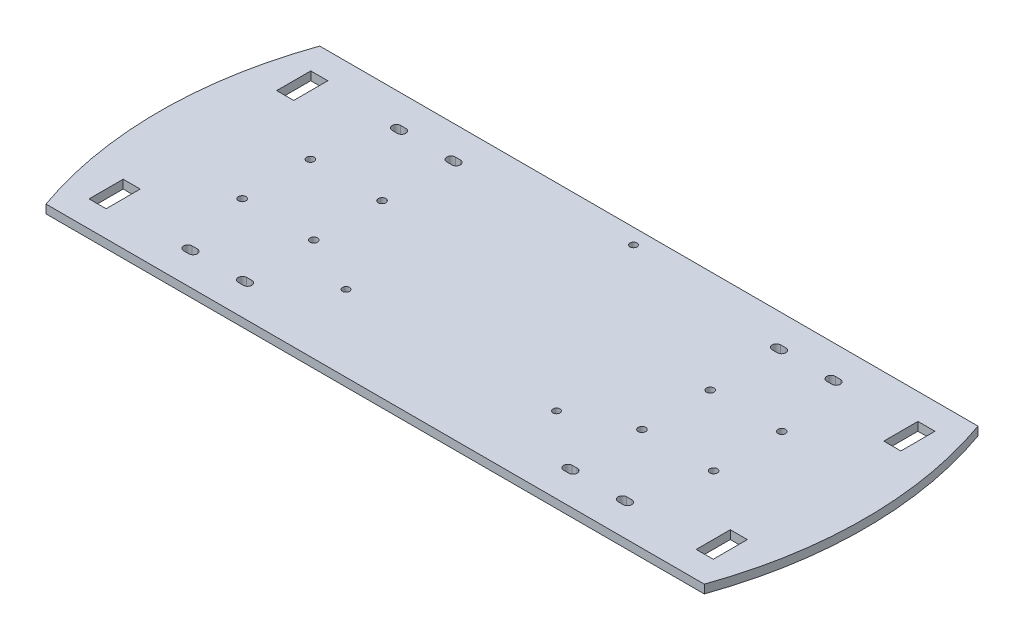
SolidWorks part; units mm, degrees
ref_plane "前基準面" through (0, 0, 0) normal (0, 0, 1) x (1, 0, 0)
ref_plane "上基準面" through (0, 0, 0) normal (0, 1, 0) x (1, 0, 0)
ref_plane "右基準面" through (0, 0, 0) normal (1, 0, 0) x (0, 0, -1)
sketch "草圖1" plane through (0, 0, 0) normal (0, 1, 0) x (1, 0, 0)
  line L0 (0, 0) -> (0, 89.692) construction
  line L1 (0, 0) -> (84.1488, -48.5834) construction
  line L2 (0, 0) -> (-79.0259, -45.6256) construction
  line L3 (183, -45) -> (173, -45)
  line L4 (193, -80.25) -> (-193, -80.25)
  line L5 (193, -80.25) -> (193, 80.25) construction
  line L6 (193, 80.25) -> (-193, 80.25)
  line L7 (-193, -80.25) -> (-193, 80.25) construction
  line L8 (0, 80.25) -> (0, -80.25) construction
  line L9 (193, 0) -> (-193, 0) construction
  line L10 (-155, -100) -> (155, -100) construction
  line L11 (-155, -100) -> (-155, 100) construction
  line L12 (-155, 100) -> (155, 100) construction
  line L13 (155, -100) -> (155, 100) construction
  line L14 (0, 100) -> (0, -100) construction
  line L15 (-155, 0) -> (155, 0) construction
  line L16 (-156, -22) -> (-172, -22) construction
  line L17 (-156, -22) -> (-156, 22) construction
  line L18 (-156, 22) -> (-172, 22) construction
  line L19 (-172, -22) -> (-172, 22) construction
  line L20 (-173, -80) -> (-183, -80) construction
  line L21 (-156, 0) -> (-172, 0) construction
  line L22 (-173, -80) -> (-173, 80) construction
  line L23 (-173, 80) -> (-183, 80) construction
  line L24 (-183, -80) -> (-183, 80) construction
  line L25 (-183, -65) -> (-173, -65)
  line L26 (-173, 0) -> (-183, 0) construction
  line L27 (-183, -65) -> (-183, -45)
  line L28 (-183, -45) -> (-173, -45)
  line L29 (-173, -65) -> (-173, -45)
  line L30 (-183, 45) -> (-173, 45)
  line L31 (-183, 45) -> (-183, 65)
  line L32 (-183, 65) -> (-173, 65)
  line L33 (-173, 45) -> (-173, 65)
  line L34 (173, -65) -> (173, -45)
  line L35 (183, -65) -> (173, -65)
  line L36 (183, -65) -> (183, -45)
  line L37 (183, 65) -> (173, 65)
  line L38 (173, 45) -> (173, 65)
  line L39 (183, 45) -> (173, 45)
  line L40 (183, 45) -> (183, 65)
  circle A0 centre (0, 71.25) radius 4 construction
  circle A4 centre (61.7043, -35.625) radius 4 construction
  circle A6 centre (-61.7043, -35.625) radius 4 construction
  circle A7 centre (0, 71.25) radius 2.05
  circle A8 centre (61.7043, -35.625) radius 2.05
  circle A9 centre (-61.7043, -35.625) radius 2.05
  circle A11 centre (0, 0) radius 75.25 construction
  circle A12 centre (0, 0) radius 80.25 construction
  arc A13 (-193, 80.25) -> (-193, -80.25) centre (33.1856, 0) ccw
  arc A14 (193, 80.25) -> (193, -80.25) centre (-33.1856, 0) cw
  point P22 (-164, 0)
  point P33 (-178, 0)
  point P62 (206.8144, 0)
  point P63 (-206.8144, 0)
  dimension "D3" = 4.1
  dimension "D4" = 8
  dimension "D5" = 71.25
  dimension "D6" = 120
  dimension "D1" = 120
  dimension "D9" = 5
  dimension "D22" = 4.1
  dimension "D23" = 240
  dimension "D2" = 71.25
  dimension "D7" = 71.25
  dimension "D8" = 310
  dimension "D10" = 200
  dimension "D11" = 16
  dimension "D12" = 44
  dimension "D13" = 1
  dimension "D14" = 10
  dimension "D15" = 160
  dimension "D16" = 1
  dimension "D17" = 10
  dimension "D18" = 386
  dimension "D19" = 20
  dimension "D20" = 15
  dimension "D21" = 15
  dimension "D24" = 413.6287
extrude "填料-伸長1" add sketch "草圖1" along normal blind 5
sketch "草圖2" plane through (0, 5, 0) normal (0, 1, 0) x (1, 0, 0)
  line L0 (-232.8206, 0) -> (229.5414, 0) construction
  line L1 (0, 102.2006) -> (0, -106.5728) construction
  line L2 (-54.2, 28.5) -> (-151.2, 28.5)
  line L3 (-54.2, 28.5) -> (-54.2, -28.5)
  line L4 (-54.2, -28.5) -> (-151.2, -28.5)
  line L5 (-151.2, 28.5) -> (-151.2, -28.5)
  line L6 (-102.7, -28.5) -> (-102.7, 28.5) construction
  line L7 (-54.2, 0) -> (-151.2, 0) construction
  line L8 (-173, -65) -> (-173, -45) construction
  line L9 (-172.2, 4) -> (-151.2, 4)
  line L10 (-172.2, 4) -> (-172.2, -4) construction
  line L11 (-172.2, -4) -> (-151.2, -4)
  line L12 (-151.2, 4) -> (-151.2, -4)
  line L13 (-172, 15) -> (-154.9, 15)
  line L14 (-172.2, 0) -> (-151.2, 0) construction
  line L15 (-172, 15) -> (-172, -15)
  line L16 (-172, -15) -> (-154.9, -15)
  line L17 (-154.9, 15) -> (-154.9, -15)
  line L18 (172, -15) -> (154.9, -15)
  line L19 (154.9, 15) -> (154.9, -15)
  line L20 (172, 15) -> (154.9, 15)
  line L21 (172, 15) -> (172, -15)
  line L22 (172.2, -4) -> (151.2, -4)
  line L23 (151.2, 4) -> (151.2, -4)
  line L24 (172.2, 4) -> (151.2, 4)
  line L25 (172.2, 4) -> (172.2, -4)
  line L26 (54.2, -28.5) -> (151.2, -28.5)
  line L27 (151.2, 28.5) -> (151.2, -28.5)
  line L28 (54.2, 28.5) -> (151.2, 28.5)
  line L29 (54.2, 28.5) -> (54.2, -28.5)
  line L30 (193, 80.25) -> (-193, 80.25) construction
  line L31 (-183, 80.25) -> (-173, 80.25) construction
  line L32 (-183, 80.25) -> (-183, -80.25) construction
  line L33 (-183, -80.25) -> (-173, -80.25) construction
  line L34 (-173, 80.25) -> (-173, -80.25) construction
  line L35 (-193, -80.25) -> (193, -80.25) construction
  line L36 (-183, 65) -> (-183, 45) construction
  line L37 (183, 80.25) -> (183, -80.25) construction
  line L38 (173, 80.25) -> (173, -80.25) construction
  point P3 (-102.7, 0)
  point P9 (-160.2566, 0)
  point P16 (-172, 0)
  dimension "D1" = 97
  dimension "D2" = 57
  dimension "D3" = 21
  dimension "D4" = 8
  dimension "D5" = 30
  dimension "D6" = 17.1
  dimension "D7" = 20.8
  dimension "D8" = 1
  dimension "D9" = 10
sketch "草圖4" plane through (0, 5, 0) normal (0, 1, 0) x (1, 0, 0)
  line L0 (0, 102.2006) -> (0, -106.5728) construction
  line L1 (-86.2, -32.5) -> (-154.2, -32.5) construction
  line L2 (-86.2, -32.5) -> (-86.2, 32.5) construction
  line L3 (-86.2, 32.5) -> (-154.2, 32.5) construction
  line L4 (-154.2, -32.5) -> (-154.2, 32.5) construction
  line L5 (-232.8206, 0) -> (229.5414, 0) construction
  line L6 (-151.2, 32.5) -> (-151.2, -32.5) construction
  line L7 (-151.2, 28.5) -> (-151.2, -28.5) construction
  line L8 (-138.2, -20) -> (-96.2, -20) construction
  line L9 (-138.2, -17.9) -> (-96.2, -17.9) construction
  line L10 (-138.2, -22.1) -> (-96.2, -22.1) construction
  line L11 (-232.8206, 0) -> (229.5414, 0) construction
  line L12 (-138.2, 20) -> (-96.2, 20) construction
  line L13 (-138.2, 17.9) -> (-96.2, 17.9) construction
  line L14 (-138.2, 22.1) -> (-96.2, 22.1) construction
  line L15 (-138.2, 20) -> (-138.2, -20) construction
  line L16 (-136, 20) -> (-136, -20) construction
  line L17 (-140.4, 20) -> (-140.4, -20) construction
  line L18 (-96.2, 20) -> (-96.2, -20) construction
  line L19 (-94, 20) -> (-94, -20) construction
  line L20 (-98.4, 20) -> (-98.4, -20) construction
  line L21 (-173, 80.25) -> (-173, -80.25) construction
  line L22 (0, 102.2006) -> (0, -106.5728) construction
  line L23 (-96.9, 61.15) -> (-93.9, 61.15) construction
  line L24 (-96.9, 63.65) -> (-93.9, 63.65)
  line L25 (-96.9, 58.65) -> (-93.9, 58.65)
  line L26 (-128.9, 61.15) -> (-125.9, 61.15) construction
  line L27 (-128.9, 63.65) -> (-125.9, 63.65)
  line L28 (-128.9, 58.65) -> (-125.9, 58.65)
  line L29 (-83.8, 70.25) -> (-139, 70.25) construction
  line L30 (-83.8, 70.25) -> (-83.8, 52.05) construction
  line L31 (-83.8, 52.05) -> (-139, 52.05) construction
  line L32 (-139, 70.25) -> (-139, 52.05) construction
  line L33 (-111.4, 52.05) -> (-111.4, 70.25) construction
  line L34 (-83.8, 61.15) -> (-139, 61.15) construction
  line L35 (193, 80.25) -> (-193, 80.25) construction
  line L36 (-96.9, -61.15) -> (-93.9, -61.15) construction
  line L37 (-96.9, -63.65) -> (-93.9, -63.65)
  line L38 (-96.9, -58.65) -> (-93.9, -58.65)
  line L39 (-128.9, -61.15) -> (-125.9, -61.15) construction
  line L40 (-128.9, -63.65) -> (-125.9, -63.65)
  line L41 (-128.9, -58.65) -> (-125.9, -58.65)
  line L42 (-83.8, -70.25) -> (-83.8, -52.05) construction
  line L43 (-83.8, -70.25) -> (-139, -70.25) construction
  line L44 (-139, -70.25) -> (-139, -52.05) construction
  line L45 (-83.8, -52.05) -> (-139, -52.05) construction
  line L46 (96.9, -61.15) -> (93.9, -61.15) construction
  line L47 (96.9, -63.65) -> (93.9, -63.65)
  line L48 (96.9, -58.65) -> (93.9, -58.65)
  line L49 (128.9, -61.15) -> (125.9, -61.15) construction
  line L50 (128.9, -63.65) -> (125.9, -63.65)
  line L51 (128.9, -58.65) -> (125.9, -58.65)
  line L52 (96.9, 61.15) -> (93.9, 61.15) construction
  line L53 (96.9, 63.65) -> (93.9, 63.65)
  line L54 (96.9, 58.65) -> (93.9, 58.65)
  line L55 (128.9, 61.15) -> (125.9, 61.15) construction
  line L56 (128.9, 63.65) -> (125.9, 63.65)
  line L57 (128.9, 58.65) -> (125.9, 58.65)
  line L58 (83.8, 61.15) -> (139, 61.15) construction
  line L59 (111.4, 52.05) -> (111.4, 70.25) construction
  line L60 (139, 70.25) -> (139, 52.05) construction
  line L61 (83.8, 52.05) -> (139, 52.05) construction
  line L62 (83.8, 70.25) -> (83.8, 52.05) construction
  line L63 (83.8, 70.25) -> (139, 70.25) construction
  line L64 (83.8, -52.05) -> (139, -52.05) construction
  line L65 (139, -70.25) -> (139, -52.05) construction
  line L66 (83.8, -70.25) -> (139, -70.25) construction
  line L67 (83.8, -70.25) -> (83.8, -52.05) construction
  line L68 (-173, 65) -> (-183, 65) construction
  arc A0 (-138.2, -17.9) -> (-138.2, -22.1) centre (-138.2, -20) ccw construction
  arc A1 (-96.2, -22.1) -> (-96.2, -17.9) centre (-96.2, -20) ccw construction
  arc A2 (-138.2, 17.9) -> (-138.2, 22.1) centre (-138.2, 20) cw construction
  arc A3 (-96.2, 22.1) -> (-96.2, 17.9) centre (-96.2, 20) cw construction
  arc A4 (-136, 20) -> (-140.4, 20) centre (-138.2, 20) ccw construction
  arc A5 (-140.4, -20) -> (-136, -20) centre (-138.2, -20) ccw construction
  arc A6 (-94, 20) -> (-98.4, 20) centre (-96.2, 20) ccw construction
  arc A7 (-98.4, -20) -> (-94, -20) centre (-96.2, -20) ccw construction
  circle A12 centre (-138.2, 20) radius 2.2
  circle A13 centre (-96.2, 20) radius 2.2
  circle A14 centre (-96.2, -20) radius 2.2
  circle A15 centre (-138.2, -20) radius 2.2
  circle A16 centre (96.2, -20) radius 2.2
  circle A17 centre (138.2, -20) radius 2.2
  circle A18 centre (96.2, 20) radius 2.2
  circle A19 centre (138.2, 20) radius 2.2
  arc A20 (-96.9, 63.65) -> (-96.9, 58.65) centre (-96.9, 61.15) ccw
  arc A21 (-93.9, 58.65) -> (-93.9, 63.65) centre (-93.9, 61.15) ccw
  arc A22 (-128.9, 63.65) -> (-128.9, 58.65) centre (-128.9, 61.15) ccw
  arc A23 (-125.9, 58.65) -> (-125.9, 63.65) centre (-125.9, 61.15) ccw
  arc A24 (-96.9, -63.65) -> (-96.9, -58.65) centre (-96.9, -61.15) cw
  arc A25 (-93.9, -58.65) -> (-93.9, -63.65) centre (-93.9, -61.15) cw
  arc A26 (-128.9, -63.65) -> (-128.9, -58.65) centre (-128.9, -61.15) cw
  arc A27 (-125.9, -58.65) -> (-125.9, -63.65) centre (-125.9, -61.15) cw
  arc A28 (96.9, -63.65) -> (96.9, -58.65) centre (96.9, -61.15) ccw
  arc A29 (93.9, -58.65) -> (93.9, -63.65) centre (93.9, -61.15) ccw
  arc A30 (128.9, -63.65) -> (128.9, -58.65) centre (128.9, -61.15) ccw
  arc A31 (125.9, -58.65) -> (125.9, -63.65) centre (125.9, -61.15) ccw
  arc A32 (96.9, 63.65) -> (96.9, 58.65) centre (96.9, 61.15) cw
  arc A33 (93.9, 58.65) -> (93.9, 63.65) centre (93.9, 61.15) cw
  arc A34 (128.9, 63.65) -> (128.9, 58.65) centre (128.9, 61.15) cw
  arc A35 (125.9, 58.65) -> (125.9, 63.65) centre (125.9, 61.15) cw
  point P4 (-86.2, 0)
  point P13 (-117.2, -20)
  point P18 (-138.2, 0)
  point P21 (-117.2, 20)
  point P32 (-96.2, 0)
  point P43 (-95.4, 61.15)
  point P63 (-127.4, 61.15)
  point P71 (-123.4, 61.15)
  point P72 (-99.4, 61.15)
  point P73 (-131.4, 61.15)
  point P74 (-91.4, 61.15)
  point P80 (-111.4, 61.15)
  point P98 (-95.4, -61.15)
  point P105 (-127.4, -61.15)
  point P116 (95.4, -61.15)
  point P123 (127.4, -61.15)
  point P130 (95.4, 61.15)
  point P137 (127.4, 61.15)
  point P150 (111.4, 61.15)
  dimension "D7" = 2.1
  dimension "D8" = 2.2
  dimension "D9" = 4.4
  dimension "D1" = 68
  dimension "D2" = 65
  dimension "D3" = 3
  dimension "D4" = 42
  dimension "D5" = 10
  dimension "D6" = 40
  dimension "D10" = 5
  dimension "D11" = 24
  dimension "D12" = 40
  dimension "D13" = 34
  dimension "D14" = 7.6
  dimension "D15" = 18.2
  dimension "D16" = 10
extrude "除料-伸長1" cut sketch "草圖4" against normal through all
